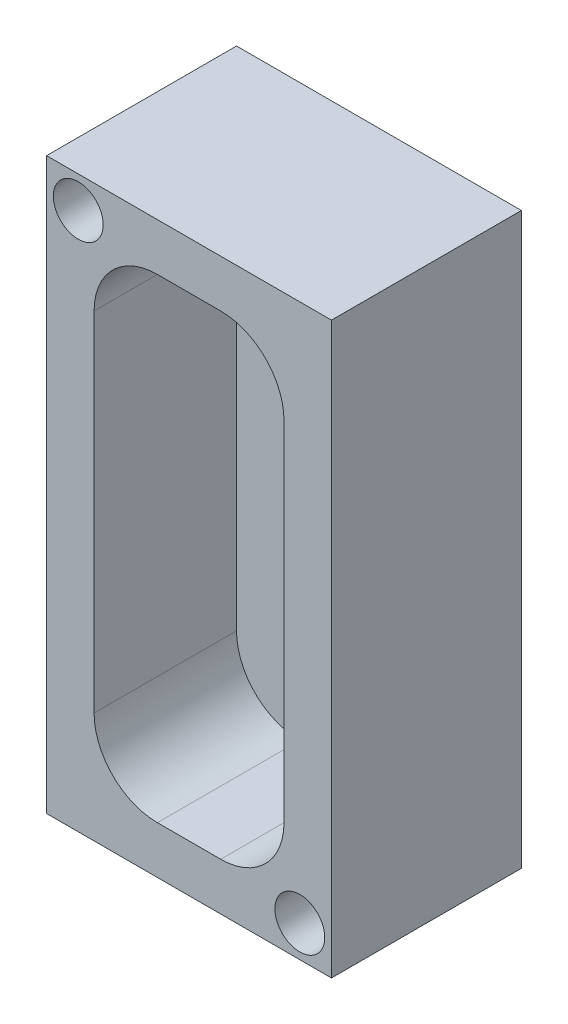
SolidWorks part; units mm, degrees
ref_plane "Front Plane" through (0, 0, 0) normal (0, 0, 1) x (1, 0, 0)
ref_plane "Top Plane" through (0, 0, 0) normal (0, 1, 0) x (1, 0, 0)
ref_plane "Right Plane" through (0, 0, 0) normal (1, 0, 0) x (0, 0, -1)
sketch "Sketch1" plane through (0, 0, 0) normal (0, 0, 1) x (1, 0, 0)
  line L0 (0, -6.6) -> (0, 6.6) construction
  line L1 (-9, -18) -> (9, -18)
  line L2 (-9, -18) -> (-9, 18)
  line L3 (-9, 18) -> (9, 18)
  line L4 (9, -18) -> (9, 18)
  line L5 (-9, -18) -> (9, 18) construction
  line L6 (-9, 18) -> (9, -18) construction
  line L7 (0, 18) -> (0, 12) construction
  line L8 (0, 12) -> (0, 6) construction
  line L9 (0, 6) -> (0, 0) construction
  line L10 (0, 0) -> (0, -6) construction
  line L11 (0, -6) -> (0, -12) construction
  line L12 (0, -12) -> (0, -18) construction
  circle A0 centre (0, 12) radius 2.525
  circle A1 centre (0, 0) radius 2.525
  circle A2 centre (0, -12) radius 2.525
  point P0 (0, 0)
  point P17 (50.0793, -178.7143)
  point P19 (53.0251, -81.5016)
  point P20 (41.246, -40.3531)
  dimension "D1" = 5.05
  dimension "D2" = 18
  dimension "D3" = 36
extrude "Boss-Extrude1" add sketch "Sketch1" along normal blind 12 contours A1 | A2 | L1 L4 L3 L2 A2 A1 A0 | A0 region at (-8.5975, 0, 0) region at (0, 12, 0) region at (0, 0, 0) region at (0, -12, 0)
shell "Shell1" thickness 3 removed face at (0, 0, 12)
extrude "Cut-Extrude1" cut sketch "Sketch1<3>" along normal blind 10 contours A0 | A1 | A2 region at (0, 12, 0) region at (0, 0, 0) region at (0, -12, 0)
sketch "Sketch1<3>" plane through (0, 0, 0) normal (0, 0, 1) x (1, 0, 0) same geometry as "Sketch1"
sketch "Sketch2" plane through (0, 0, 3) normal (0, 0, 1) x (1, 0, 0)
  circle A0 centre (0, 12) radius 2.925
  circle A1 centre (0, 0) radius 2.925
  circle A2 centre (0, -12) radius 2.925
  dimension "D1" = 5.85
extrude "Cut-Extrude2" cut sketch "Sketch2" against normal blind 1
fillet "Fillet1" radius 4 4 edges at (-6, 15, 7.5) (6, 15, 7.5) (-6, -15, 7.5) (6, -15, 7.5)
hole_wizard "Tap Drill for M3 Helicoil1" positions "Sketch7" profile "Sketch9" hole size "M3x0.5" standard "ANSI Metric"
sketch "Sketch7" plane through (0, 0, 12) normal (0, 0, 1) x (1, 0, 0)
  line L1 (-7, 16) -> (7, 16) construction
  line L2 (-7, 16) -> (-7, -16) construction
  line L3 (-7, -16) -> (7, -16) construction
  line L4 (7, 16) -> (7, -16) construction
  line L5 (-7, 16) -> (7, -16) construction
  line L6 (-7, -16) -> (7, 16) construction
  line L7 (6, -11) -> (6, 11) construction
  line L8 (-2, 15) -> (2, 15) construction
  point P0 (7, -16)
  point P2 (-7, 16)
  point P56 (0, 0)
  point P62 (0, 0)
  point P64 (-7, 16)
  dimension "D1" = 1
  dimension "D2" = 1
sketch "Sketch9" plane through (7, -16, 12) normal (1, 0, 0) x (0, -1, 0)
  line L0 (0, 0) -> (0, 4.2464)
  line L1 (0, 4.2464) -> (1.575, 3.3)
  line L2 (1.575, 3.3) -> (1.575, 0)
  line L5 (1.575, 0) -> (0, 0)
  line L10 (0, 4.2464) -> (-1.575, 3.3) construction
  line L11 (0, -6.35) -> (0, 107.95) construction
  dimension "Hole Dia." = 3.15
  dimension "Hole Depth" = 3.3
  dimension "Drill Angle" = 118
equation "\"D3@Sketch1\"=33.00mm+3"
equation "\"D2@Sketch1\"=15.00mm+3"
